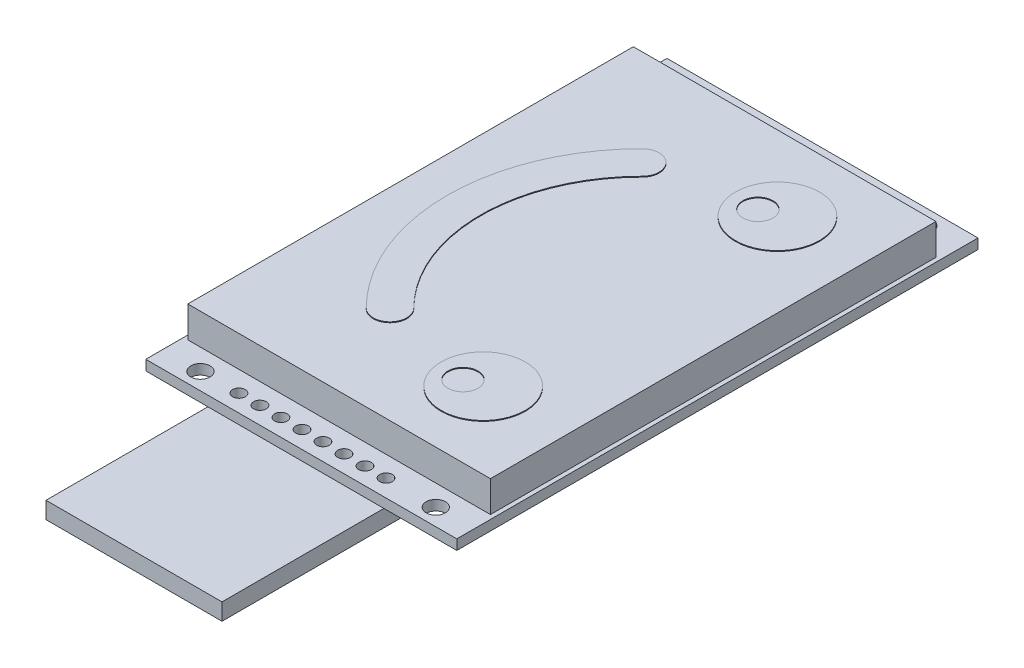
SolidWorks part; units mm, degrees
ref_plane "Front Plane" through (0, 0, 0) normal (0, 0, 1) x (1, 0, 0)
ref_plane "Top Plane" through (0, 0, 0) normal (0, 1, 0) x (1, 0, 0)
ref_plane "Right Plane" through (0, 0, 0) normal (1, 0, 0) x (0, 0, -1)
sketch "Sketch1" plane through (0, 0, 0) normal (0, 1, 0) x (1, 0, 0)
  line L0 (32.5, 60) -> (32.5, 2) construction
  line L1 (0, 0) -> (37, 0)
  line L2 (0, 0) -> (0, 62)
  line L3 (0, 62) -> (37, 62)
  line L4 (37, 0) -> (37, 62)
  line L5 (32.5, 2) -> (4.5, 2) construction
  line L6 (4.5, 2) -> (4.5, 60) construction
  line L7 (4.5, 60) -> (32.5, 60) construction
  line L8 (18.5, 2) -> (18.5, 0) construction
  line L9 (4.5, 31) -> (0, 31) construction
  circle A0 centre (32.5, 60) radius 1.15
  circle A1 centre (4.5, 60) radius 1.15
  circle A2 centre (32.5, 2) radius 1.15
  circle A3 centre (4.5, 2) radius 1.15
  dimension "D3" = 2.3
  dimension "D1" = 37
  dimension "D2" = 62
  dimension "D4" = 28
  dimension "D5" = 58
extrude "Boss-Extrude1" add sketch "Sketch1" along normal blind 1.2
sketch "Sketch2" plane through (0, 1.2, 0) normal (0, 1, 0) x (1, 0, 0)
  line L0 (37, 0) -> (37, 62) construction
  line L1 (0.5, 57.5) -> (36.5, 57.5)
  line L2 (0.5, 57.5) -> (0.5, 4.5)
  line L3 (0.5, 4.5) -> (36.5, 4.5)
  line L4 (36.5, 57.5) -> (36.5, 4.5)
  line L5 (0, 62) -> (0, 0) construction
  line L6 (36.5, 31) -> (37, 31) construction
  dimension "D1" = 0.5
  dimension "D2" = 0.5
  dimension "D3" = 53
extrude "Boss-Extrude2" add sketch "Sketch2" along normal blind 3.7
sketch "Sketch3" plane through (0, 1.2, 0) normal (0, 1, 0) x (1, 0, 0)
  circle A0 centre (9.0316, 2.0507) radius 0.75
  circle A1 centre (11.5316, 2.0507) radius 0.75
  circle A2 centre (14.0316, 2.0507) radius 0.75
  circle A3 centre (16.5316, 2.0507) radius 0.75
  circle A4 centre (19.0316, 2.0507) radius 0.75
  circle A5 centre (21.5316, 2.0507) radius 0.75
  circle A6 centre (24.0316, 2.0507) radius 0.75
  circle A7 centre (26.5316, 2.0507) radius 0.75
  dimension "D1" = 1.5
  dimension "D2" = 8
extrude "Cut-Extrude1" cut sketch "Sketch3" against normal through all
sketch "Sketch4" plane through (0, 4.9, 0) normal (0, 1, 0) x (1, 0, 0)
  line L0 (26.6399, 48.5) -> (26.6399, 13.5) construction
  line L1 (13.0544, 46) -> (13.0544, 16) construction
  line L2 (26.6399, 31) -> (13.0544, 31) construction
  line L3 (36.5, 31) -> (26.6399, 31) construction
  line L4 (36.5, 4.5) -> (36.5, 57.5) construction
  circle A0 centre (26.6399, 48.5) radius 5
  circle A1 centre (26.6399, 13.5) radius 5
  arc A2 (11.6401, 47.4142) -> (11.6401, 14.5858) centre (28.0544, 31) ccw
  arc A3 (14.4686, 44.5858) -> (14.4686, 17.4142) centre (28.0544, 31) ccw
  arc A4 (14.4686, 44.5858) -> (11.6401, 47.4142) centre (13.0544, 46) ccw
  arc A5 (14.4686, 17.4142) -> (11.6401, 14.5858) centre (13.0544, 16) cw
  circle A6 centre (24.7633, 12.9717) radius 1.7861
  circle A7 centre (24.7633, 48.0582) radius 1.7861
  dimension "D1" = 35
  dimension "D2" = 10
  dimension "D4" = 2
  dimension "D3" = 30
  dimension "D5" = 15
extrude "Boss-Extrude3" add sketch "Sketch4" along normal blind 0.1
ref_plane "Plane1" through (0, 0, -31) normal (0, 0, 1) x (1, 0, 0)
sketch "Sketch5" plane through (0, 0, 0) normal (0, -1, 0) x (1, 0, 0)
  line L1 (7.392, -4.4911) -> (28.3291, -4.4911)
  line L2 (7.392, -4.4911) -> (7.392, 19.2584)
  line L3 (7.392, 19.2584) -> (28.3291, 19.2584)
  line L4 (28.3291, -4.4911) -> (28.3291, 19.2584)
  point P4 (28.3291, 19.2584)
extrude "Boss-Extrude4" add sketch "Sketch5" along normal blind 2
